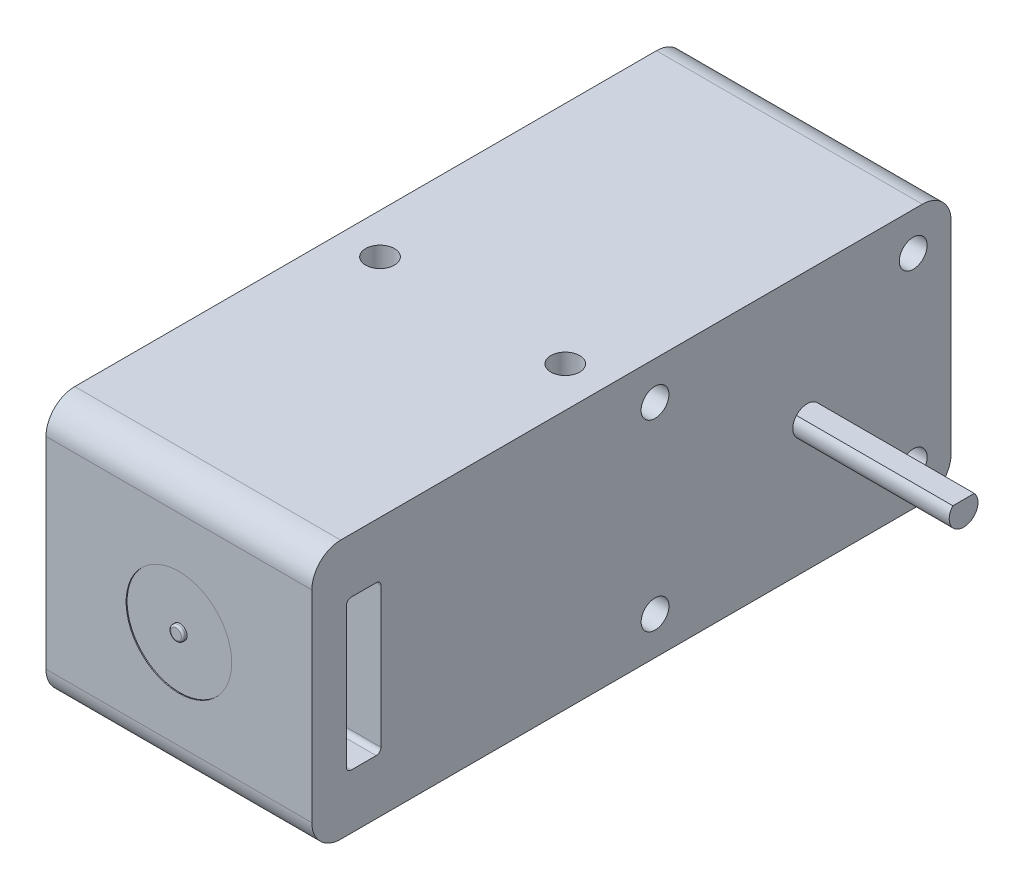
SolidWorks part; units mm, degrees
ref_plane "Front Plane" through (0, 0, 0) normal (0, 0, 1) x (1, 0, 0)
ref_plane "Top Plane" through (0, 0, 0) normal (0, 1, 0) x (1, 0, 0)
ref_plane "Right Plane" through (0, 0, 0) normal (1, 0, 0) x (0, 0, -1)
sketch "Sketch1" plane through (0, 0, 0) normal (1, 0, 0) x (0, 0, -1)
  line L0 (-52.1286, -4.2716) -> (37.8705, -4.2716) construction
  line L1 (-42.7037, 9.2284) -> (23.8963, 9.2284)
  line L2 (-42.7037, 9.2284) -> (-42.7037, -17.7716)
  line L3 (-42.7037, -17.7716) -> (23.8963, -17.7716)
  line L4 (23.8963, 9.2284) -> (23.8963, -17.7716)
  line L5 (-39.1037, 3.5284) -> (-35.5037, 3.5284)
  line L6 (-39.1037, 3.5284) -> (-39.1037, -12.0716)
  line L7 (-39.1037, -12.0716) -> (-35.5037, -12.0716)
  line L8 (-35.5037, 3.5284) -> (-35.5037, -12.0716)
  circle A0 centre (19.9463, 5.2784) radius 1.45
  circle A1 centre (-6.9537, 5.2784) radius 1.45
  circle A2 centre (19.9463, -13.8216) radius 1.45
  circle A3 centre (-6.9537, -13.8216) radius 1.45
  circle A4 centre (8.8963, -4.2716) radius 1.5
  point P12 (-39.1037, -4.2716)
  point P13 (-42.7037, -4.2716)
  dimension "D3" = 3.95
  dimension "D5" = 26.9
  dimension "D10" = 15
  dimension "D1" = 66.6
  dimension "D2" = 27
  dimension "D4" = 3.95
  dimension "D6" = 3.95
  dimension "D7" = 3.6
  dimension "D8" = 15.6
  dimension "D9" = 3.6
extrude "Boss-Extrude1" add sketch "Sketch1" along normal blind 27.7 contours L0 L2 L3 L4 A4 L8 L7 L6 A3 A2 | L2 L0 L6 L5 L8 A4 L4 L1 A0 A1 region at (0, 2.5541, 8.8082) region at (0, -11.0973, 8.8082)
fillet "Fillet1" radius 3 4 edges at (13.85, -17.7716, -23.8963) (13.85, -17.7716, 42.7037) (13.85, 9.2284, -23.8963) (13.85, 9.2284, 42.7037)
fillet "Fillet2" radius 0.5 4 edges at (13.85, -12.0716, 35.5037) (13.85, -12.0716, 39.1037) (13.85, 3.5284, 39.1037) (13.85, 3.5284, 35.5037)
sketch "Sketch2" plane through (0, 9.2284, 0) normal (0, 1, 0) x (1, 0, 0)
  line L0 (0, 23.8963) -> (27.7, 23.8963) construction
  line L1 (0, -39.7037) -> (0, 20.8963) construction
  line L2 (27.7, -39.7037) -> (27.7, 20.8963) construction
  circle A0 centre (4.2, -12.1037) radius 1.5
  circle A1 centre (23.5, -12.1037) radius 1.5
  point P8 (0, 0)
  dimension "D1" = 36
  dimension "D2" = 4.2
  dimension "D3" = 4.2
extrude "Cut-Extrude1" cut sketch "Sketch2" against normal blind 27.7
sketch "Sketch3" plane through (0, 0, 0) normal (1, 0, 0) x (0, 0, -1)
  line L3 (7.7783, -3.2716) -> (10.0144, -3.2716)
  circle A0 centre (8.8963, -4.2716) radius 1.5 construction
  circle A1 centre (8.8963, -4.2716) radius 1.5
  point P4 (0, 0)
  dimension "D1" = 1
extrude "Boss-Extrude2" add sketch "Sketch3" against normal blind 10.6 separate body contours L3 A1 region at (0, -4.4196, -8.8963)
extrude "Boss-Extrude3" add sketch "Sketch3<4>" along normal blind 44 contours L3 A1 region at (0, -4.4196, -8.8963)
sketch "Sketch3<4>" plane through (0, 0, 0) normal (1, 0, 0) x (0, 0, -1) same geometry as "Sketch3"
sketch "Sketch4" plane through (0, 0, 39.1037) normal (0, 0, -1) x (-1, 0, 0)
  line L0 (0, 6.2284) -> (-27.7, 6.2284) construction
  line L1 (-27.7, 6.2284) -> (-27.7, -14.7716) construction
  circle A0 centre (-13.85, -4.2716) radius 7.25
  point P4 (-13.85, 6.2284)
  point P7 (-27.7, -4.2716)
extrude "Boss-Extrude4" add sketch "Sketch4" along normal blind 19
sketch "Sketch5" plane through (0, 0, 42.7037) normal (0, 0, 1) x (1, 0, 0)
  line L0 (27.7, 6.2284) -> (0, 6.2284) construction
  line L1 (0, -3.2716) -> (0, -5.7716) construction
  circle A0 centre (13.85, -4.5216) radius 5.5
  point P2 (0, 0)
  point P5 (13.85, 6.2284)
  point P8 (0, -4.5216)
extrude "Cut-Extrude2" cut sketch "Sketch5" against normal blind 0.1
sketch "Sketch6" plane through (0, 0, 42.6037) normal (0, 0, 1) x (1, 0, 0)
  circle A0 centre (13.85, -4.5216) radius 0.75
  circle A1 centre (13.85, -4.5216) radius 5.5 construction
extrude "Boss-Extrude6" add sketch "Sketch6" along normal blind 0.4
fillet "Fillet3" radius 0.2 1 edges at (14.6, -4.5216, 43.0037)
